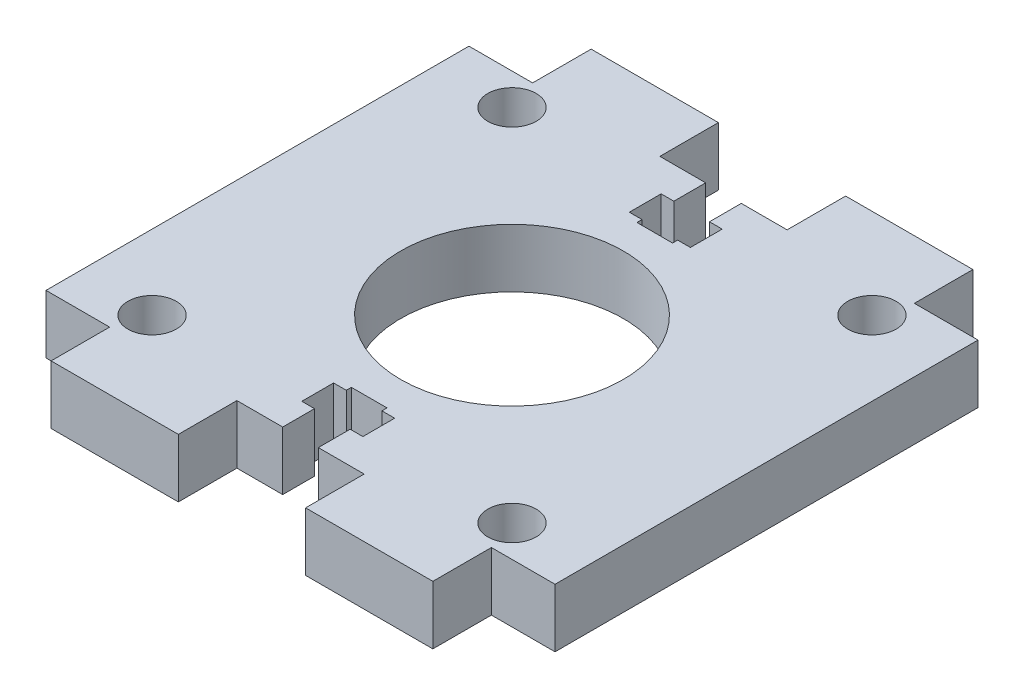
SolidWorks part; units mm, degrees
ref_plane "Front Plane" through (0, 0, 0) normal (0, 0, 1) x (1, 0, 0)
ref_plane "Top Plane" through (0, 0, 0) normal (0, 1, 0) x (1, 0, 0)
ref_plane "Right Plane" through (0, 0, 0) normal (1, 0, 0) x (0, 0, -1)
sketch "Sketch1" plane through (0, 0, 0) normal (0, 1, 0) x (1, 0, 0)
  line L0 (0, 21.1058) -> (0, -21.1058) construction
  line L1 (25.4, -21.1058) -> (19.05, -21.1058)
  line L2 (25.4, -21.1058) -> (25.4, 21.1058)
  line L3 (25.4, 21.1058) -> (19.05, 21.1058)
  line L4 (-25.4, -21.1058) -> (-25.4, 21.1058)
  line L5 (25.4, -21.1058) -> (-25.4, 21.1058) construction
  line L6 (25.4, 21.1058) -> (-25.4, -21.1058) construction
  line L7 (-19.05, -21.1058) -> (-25.4, -21.1058)
  line L8 (-6.35, -26.9478) -> (-19.05, -26.9478)
  line L9 (-6.35, -26.9478) -> (-6.35, -21.1058)
  line L10 (-25.4, 0) -> (25.4, 0) construction
  line L11 (-19.05, -26.9478) -> (-19.05, -21.1058)
  line L12 (-6.35, -26.9478) -> (-19.05, -21.1058) construction
  line L13 (-6.35, -21.1058) -> (-19.05, -26.9478) construction
  line L14 (6.35, -21.1058) -> (19.05, -26.9478) construction
  line L15 (6.35, -26.9478) -> (19.05, -21.1058) construction
  line L16 (19.05, -26.9478) -> (19.05, -21.1058)
  line L17 (6.35, -26.9478) -> (6.35, -21.1058)
  line L18 (6.35, -26.9478) -> (19.05, -26.9478)
  line L19 (-25.4, 21.1058) -> (25.4, -21.1058) construction
  line L20 (6.35, -21.1058) -> (1.778, -21.1058)
  line L21 (6.35, 26.9478) -> (19.05, 21.1058) construction
  line L22 (6.35, 21.1058) -> (19.05, 26.9478) construction
  line L23 (-6.35, 21.1058) -> (-19.05, 26.9478) construction
  line L24 (-6.35, 26.9478) -> (-19.05, 21.1058) construction
  line L25 (6.35, 21.1058) -> (1.778, 21.1058)
  line L26 (6.35, 26.9478) -> (19.05, 26.9478)
  line L27 (6.35, 26.9478) -> (6.35, 21.1058)
  line L28 (19.05, 26.9478) -> (19.05, 21.1058)
  line L29 (-19.05, 26.9478) -> (-19.05, 21.1058)
  line L30 (-6.35, 26.9478) -> (-6.35, 21.1058)
  line L31 (-6.35, 26.9478) -> (-19.05, 26.9478)
  line L32 (-19.05, 21.1058) -> (-25.4, 21.1058)
  line L33 (6.35, 21.1058) -> (1.778, 21.1058)
  line L34 (-1.778, -14.7558) -> (-3.048, -14.7558)
  line L35 (-1.778, -17.9308) -> (-3.048, -17.9308)
  line L36 (1.778, -17.9308) -> (1.778, -21.1058)
  line L37 (1.778, 14.7558) -> (-1.778, 14.2478) construction
  line L38 (-1.778, -17.9308) -> (-1.778, -21.1058)
  line L39 (1.778, -17.9308) -> (-1.778, -21.1058) construction
  line L40 (1.778, -21.1058) -> (-1.778, -17.9308) construction
  line L41 (3.048, -14.7558) -> (1.778, -14.7558)
  line L42 (3.048, -14.7558) -> (3.048, -17.9308)
  line L43 (3.048, -17.9308) -> (1.778, -17.9308)
  line L44 (-3.048, -14.7558) -> (-3.048, -17.9308)
  line L45 (3.048, -14.7558) -> (-3.048, -17.9308) construction
  line L46 (3.048, -17.9308) -> (-3.048, -14.7558) construction
  line L47 (1.778, -14.2478) -> (-1.778, -14.2478)
  line L48 (1.778, -14.2478) -> (1.778, -14.7558)
  line L49 (-1.778, -21.1058) -> (-6.35, -21.1058)
  line L50 (-1.778, -14.2478) -> (-1.778, -14.7558)
  line L51 (1.778, -14.2478) -> (-1.778, -14.7558) construction
  line L52 (1.778, -14.7558) -> (-1.778, -14.2478) construction
  line L53 (0, 7.3323) -> (-6.35, 3.6662) construction
  line L54 (-6.35, 3.6662) -> (-6.35, -3.6662) construction
  line L55 (-6.35, -3.6662) -> (0, -7.3323) construction
  line L56 (0, -7.3323) -> (6.35, -3.6662) construction
  line L57 (6.35, -3.6662) -> (6.35, 3.6662) construction
  line L58 (6.35, 3.6662) -> (0, 7.3323) construction
  line L59 (1.778, 14.2478) -> (-1.778, 14.7558) construction
  line L60 (3.048, 17.9308) -> (-3.048, 14.7558) construction
  line L61 (3.048, 14.7558) -> (-3.048, 17.9308) construction
  line L62 (1.778, 21.1058) -> (-1.778, 17.9308) construction
  line L63 (1.778, 17.9308) -> (-1.778, 21.1058) construction
  line L64 (-1.778, 14.2478) -> (-1.778, 14.7558)
  line L65 (1.778, 14.2478) -> (1.778, 14.7558)
  line L66 (1.778, 14.2478) -> (-1.778, 14.2478)
  line L67 (-3.048, 14.7558) -> (-3.048, 17.9308)
  line L68 (3.048, 17.9308) -> (1.778, 17.9308)
  line L69 (3.048, 14.7558) -> (3.048, 17.9308)
  line L70 (3.048, 14.7558) -> (1.778, 14.7558)
  line L71 (-1.778, 17.9308) -> (-1.778, 21.1058)
  line L72 (1.778, 17.9308) -> (1.778, 21.1058)
  line L73 (-1.778, 17.9308) -> (-3.048, 17.9308)
  line L74 (-1.778, 14.7558) -> (-3.048, 14.7558)
  line L75 (-1.778, 21.1058) -> (-6.35, 21.1058)
  line L76 (-1.778, 21.1058) -> (-6.35, 21.1058)
  line L77 (-17.9605, 17.9605) -> (0, 0) construction
  circle A0 centre (0, 0) radius 11.1125
  circle A1 centre (0, 0) radius 9.525 construction
  circle A2 centre (0, 0) radius 6.35 construction
  circle A3 centre (0, 0) radius 25.4 construction
  circle A4 centre (-17.9605, 17.9605) radius 2.413
  circle A5 centre (17.9605, 17.9605) radius 2.413
  circle A6 centre (17.9605, -17.9605) radius 2.413
  circle A7 centre (-17.9605, -17.9605) radius 2.413
  point P0 (0, 0)
  point P8 (-12.7, -24.0268)
  point P19 (12.7, -24.0268)
  point P28 (12.7, 24.0268)
  point P29 (-12.7, 24.0268)
  point P30 (0, -19.5183)
  point P37 (0, -16.3433)
  point P42 (0, -14.5018)
  point P67 (0, 14.5018)
  point P68 (0, 16.3433)
  point P69 (0, 19.5183)
  point P82 (0, 0)
  dimension "D8" = 22.225
  dimension "D12" = 19.05
  dimension "D13" = 12.7
  dimension "D14" = 50.8
  dimension "D15" = 4.826
  dimension "D1" = 50.8
  dimension "D2" = 42.2116
  dimension "D3" = 5.842
  dimension "D4" = 12.7
  dimension "D5" = 12.7
  dimension "D6" = 3.556
  dimension "D7" = 3.175
  dimension "D9" = 3.175
  dimension "D10" = 6.096
  dimension "D11" = 0.508
  dimension "D16" = 45
  dimension "D17" = 4
extrude "Boss-Extrude1" add sketch "Sketch1" along normal blind 5.842 contours L71 L75 L30 L31 L29 L32 L4 L7 L11 L8 L9 L49 L38 L35 L44 L34 L50 L47 L48 L41 L42 L43 L36 L20 L17 L18 L16 L1 L2 L3 L28 L26 L27 L25 L72 L68 L69 L70 L65 L66 L64 L74 L67 L73 region at (22.225, 0, 20.3652)
